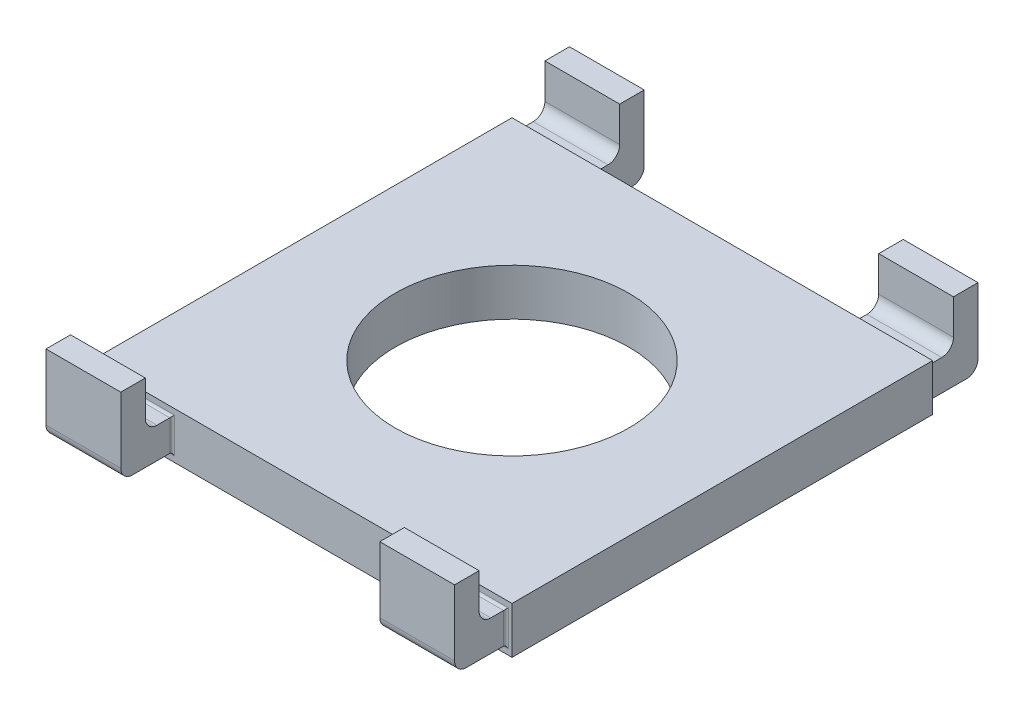
SolidWorks part; units mm, degrees
ref_plane "Front Plane" through (0, 0, 0) normal (0, 0, 1) x (1, 0, 0)
ref_plane "Top Plane" through (0, 0, 0) normal (0, 1, 0) x (1, 0, 0)
ref_plane "Right Plane" through (0, 0, 0) normal (1, 0, 0) x (0, 0, -1)
sketch "Sketch2" plane through (0, 0, 0) normal (0, 1, 0) x (1, 0, 0)
  line L1 (-22.5, 22.5) -> (22.5, 22.5)
  line L2 (-22.5, 22.5) -> (-22.5, -22.5)
  line L3 (-22.5, -22.5) -> (22.5, -22.5)
  line L4 (22.5, 22.5) -> (22.5, -22.5)
  point P0 (0, 0)
extrude "Boss-Extrude1" add sketch "Sketch2" along normal blind 5
sketch "Sketch3" plane through (0, 0, 0) normal (0, 0, 1) x (1, 0, 0)
  line L1 (-21.8536, 4.15) -> (-13.8536, 4.15)
  line L2 (-21.8536, 4.15) -> (-21.8536, 0.85)
  line L3 (-21.8536, 0.85) -> (-13.8536, 0.85)
  line L4 (-13.8536, 4.15) -> (-13.8536, 0.85)
  line L5 (-21.8536, 4.15) -> (-13.8536, 0.85) construction
  line L6 (-21.8536, 0.85) -> (-13.8536, 4.15) construction
  line L8 (0, -2.75) -> (0, 2.75) construction
  line L9 (21.8536, 4.15) -> (21.8536, 0.85)
  line L10 (21.8536, 0.85) -> (13.8536, 0.85)
  line L11 (13.8536, 4.15) -> (13.8536, 0.85)
  line L12 (21.8536, 4.15) -> (13.8536, 4.15)
  point P0 (-17.8536, 2.5)
extrude "Boss-Extrude2" add sketch "Sketch3" along normal mid plane 56
fillet "Fillet1" radius 0.25 16 edges at (-13.8536, 2.5, -22.5) (-17.8536, 4.15, -22.5) (-21.8536, 2.5, -22.5) (-17.8536, 0.85, -22.5) (17.8536, 0.85, -22.5) (13.8536, 2.5, -22.5) (21.8536, 2.5, -22.5) (17.8536, 4.15, -22.5) (21.8536, 2.5, 22.5) (17.8536, 4.15, 22.5) (17.8536, 0.85, 22.5) (13.8536, 2.5, 22.5) (-21.8536, 2.5, 22.5) (-13.8536, 2.5, 22.5) (-17.8536, 0.85, 22.5) (-17.8536, 4.15, 22.5)
sketch "Sketch4" plane through (0, 4.15, 0) normal (0, 1, 0) x (1, 0, 0)
  line L0 (-13.8536, 22.75) -> (-13.8536, 28) construction
  line L1 (-21.8536, 28) -> (-13.8536, 28)
  line L2 (-21.8536, 28) -> (-21.8536, 25.375)
  line L3 (-21.8536, 25.375) -> (-13.8536, 25.375)
  line L4 (-13.8536, 28) -> (-13.8536, 25.375)
  line L5 (21.8536, 22.75) -> (21.8536, 28) construction
  line L6 (13.8536, 28) -> (21.8536, 28)
  line L7 (13.8536, 28) -> (13.8536, 25.375)
  line L8 (13.8536, 25.375) -> (21.8536, 25.375)
  line L9 (21.8536, 28) -> (21.8536, 25.375)
  line L10 (13.8536, -28) -> (13.8536, -22.75) construction
  line L11 (21.8536, -28) -> (13.8536, -28)
  line L12 (21.8536, -28) -> (21.8536, -25.375)
  line L13 (21.8536, -25.375) -> (13.8536, -25.375)
  line L14 (13.8536, -28) -> (13.8536, -25.375)
  line L15 (-21.8536, -28) -> (-21.8536, -22.75) construction
  line L16 (-13.8536, -28) -> (-21.8536, -28)
  line L17 (-13.8536, -28) -> (-13.8536, -25.375)
  line L18 (-13.8536, -25.375) -> (-21.8536, -25.375)
  line L19 (-21.8536, -28) -> (-21.8536, -25.375)
extrude "Boss-Extrude3" add sketch "Sketch4" along normal blind 5
fillet "Fillet2" radius 1.25 8 edges at (-17.8536, 0.85, 28) (17.8536, 0.85, 28) (17.8536, 0.85, -28) (-17.8536, 0.85, -28) (17.8536, 4.15, 25.375) (-17.8536, 4.15, 25.375) (17.8536, 4.15, -25.375) (-17.8536, 4.15, -25.375)
sketch "Sketch6" plane through (0, 5, 0) normal (0, 1, 0) x (1, 0, 0)
  circle A0 centre (0, 0) radius 12.5
  dimension "D1" = 25
extrude "Cut-Extrude1" cut sketch "Sketch6" against normal blind 19
